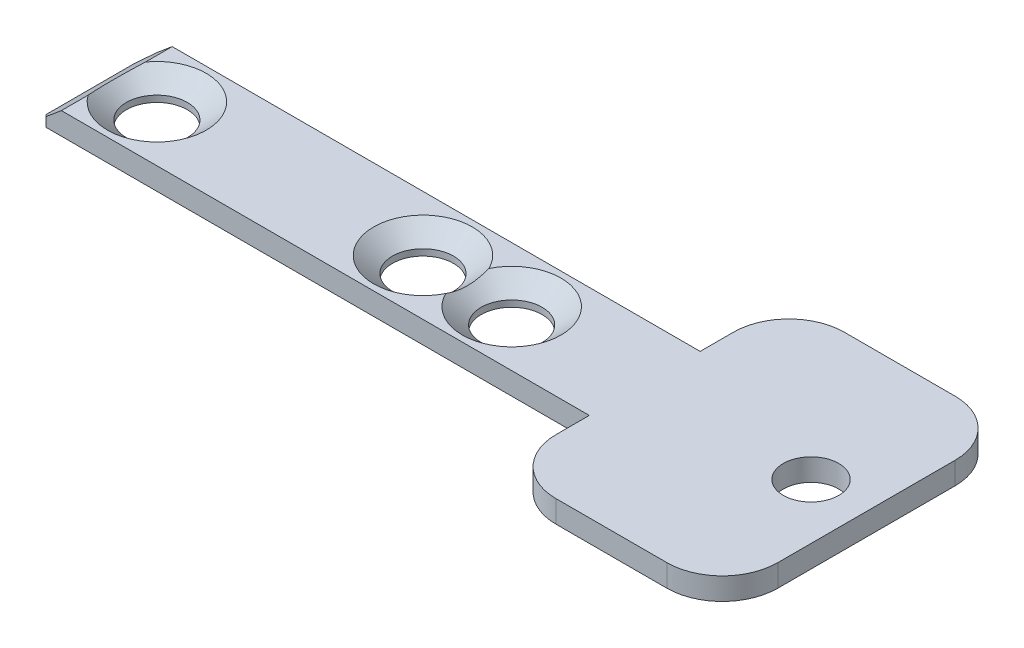
SolidWorks part; units mm, degrees
ref_plane "Front Plane" through (0, 0, 0) normal (0, 0, 1) x (1, 0, 0)
ref_plane "Top Plane" through (0, 0, 0) normal (0, 1, 0) x (1, 0, 0)
ref_plane "Right Plane" through (0, 0, 0) normal (1, 0, 0) x (0, 0, -1)
sketch "Sketch1" plane through (0, 0, 0) normal (0, 1, 0) x (1, 0, 0)
  line L0 (25, 5) -> (25, 13)
  line L1 (-25, 5) -> (25, 5)
  line L2 (-25, 5) -> (-25, -5)
  line L3 (-25, -5) -> (25, -5)
  line L5 (-25, 5) -> (25, -5) construction
  line L6 (-25, -5) -> (25, 5) construction
  line L7 (25, -13) -> (45, -13)
  line L8 (25, -13) -> (25, -5)
  line L9 (25, 13) -> (45, 13)
  line L10 (45, -13) -> (45, 13)
  point P0 (0, 0)
  dimension "D1" = 10
  dimension "D2" = 50
  dimension "D3" = 8
  dimension "D4" = 8
  dimension "D5" = 20
extrude "Boss-Extrude1" add sketch "Sketch1" along normal blind 2
chamfer "Chamfer1" distance 1 angle 45 2 edges at (-25, 1, -5) (-25, 1, 5)
fillet "Fillet1" radius 5 4 edges at (45, 1, -13) (45, 1, 13) (25, 1, 13) (25, 1, -13)
sketch "Sketch2" plane through (0, 2, 0) normal (0, 1, 0) x (1, 0, 0)
  line L0 (45, -8) -> (45, 8) construction
  circle A0 centre (40, 0) radius 2.5
  dimension "D1" = 5
  dimension "D2" = 5
extrude "Cut-Extrude1" cut sketch "Sketch2" against normal blind 3
sketch "Sketch3" plane through (0, 2, 0) normal (0, 1, 0) x (1, 0, 0)
  line L0 (25, 5) -> (25, -5) construction
  circle A0 centre (13, 0) radius 2.75
  circle A1 centre (5, 0) radius 2.75
  circle A4 centre (-19, 0) radius 2.75
  dimension "D1" = 5.5
  dimension "D2" = 5.5
  dimension "D3" = 8
  dimension "D6" = 12
  dimension "D8" = 5.5
extrude "Cut-Extrude2" cut sketch "Sketch3" against normal blind 3
chamfer "Chamfer2" distance 2 angle 50 1 edges at (-25, 2, 0) first distance on face at (-25, 1, 0)
chamfer "Chamfer3" distance 1.7 angle 40 3 edges at (13, 2, 2.75) (5, 2, 2.75) (-19, 2, 2.75) first distance on face at (-19, 2, 2.75)
